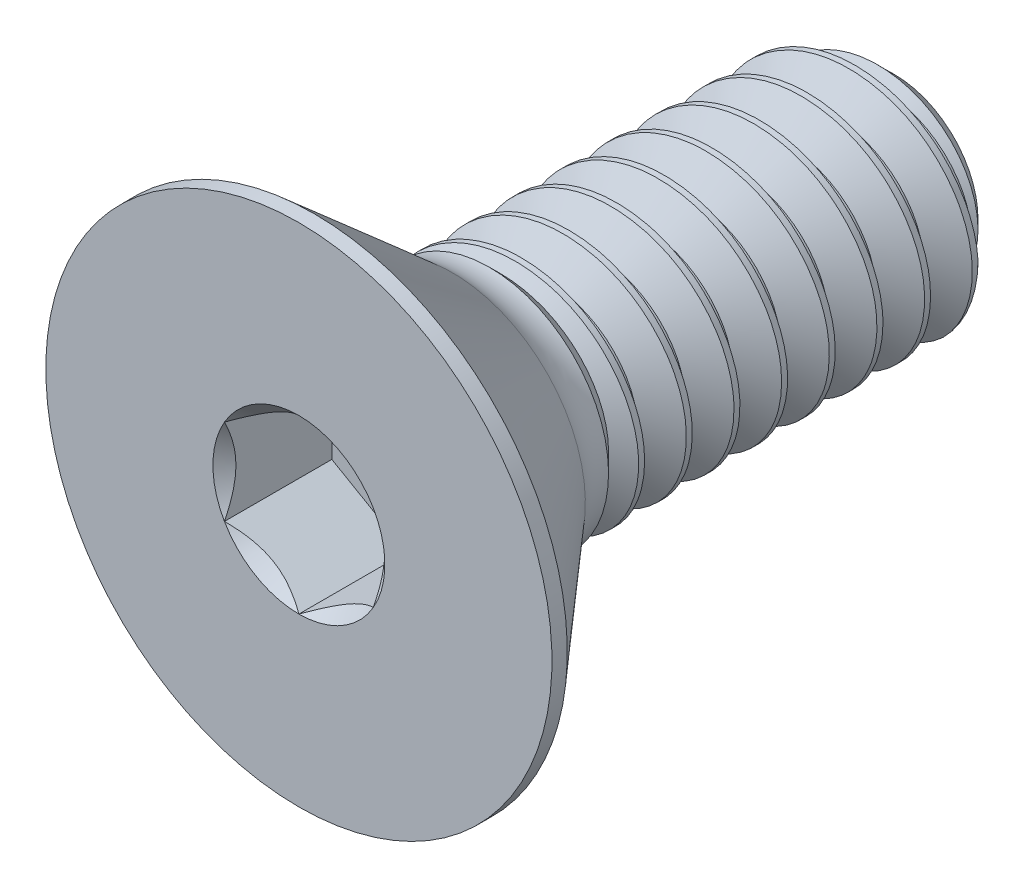
SolidWorks part; units mm, degrees
ref_plane "Front" through (0, 0, 0) normal (0, 0, 1) x (1, 0, 0)
ref_plane "Top" through (0, 0, 0) normal (0, 1, 0) x (1, 0, 0)
ref_plane "Right" through (0, 0, 0) normal (1, 0, 0) x (0, 0, -1)
sketch "Sketch1" plane through (0, 0, 0) normal (1, 0, 0) x (0, 0, -1)
  line L0 (0, 6.7437) -> (0.4089, 6.7437) construction
  line L1 (0.4089, 6.7437) -> (4.0894, 3.5443) construction
  line L2 (0, 3.175) -> (15.875, 3.175)
  line L3 (15.875, 3.175) -> (15.875, 0)
  line L4 (15.875, 0) -> (0, 0)
  line L5 (0, 0) -> (0, 6.7437) construction
  line L6 (0, 6.7437) -> (0, -6.7437) construction
  line L7 (15.875, 3.175) -> (15.875, -3.175) construction
  line L8 (0, -6.7437) -> (0.4089, -6.7437) construction
  line L9 (0.4089, -6.7437) -> (4.0894, -3.5443) construction
  line L11 (0, 3.175) -> (0, 0)
  line L12 (5.0772, 3.175) -> (5.0772, 0) construction
  arc A1 (4.0894, 3.5443) -> (5.0772, 3.175) centre (5.0772, 4.6807) ccw construction
  dimension "D1" = 0.4089
revolve "Revolve1" add sketch "Sketch1" angle 360 mid plane about L4
sketch "Sketch3" plane through (0, 0, -15.875) normal (0, 0, -1) x (-1, 0, 0)
  circle A0 centre (0, 0) radius 3.175
curve "Helix/Spiral1" pitch 1.27 height 15.875 radius 3.175 centre (0, 0, -15.875) axis (0, 0, 1) start towards (0, 1, 0)
sketch "Sketch2" plane through (0, 0, 0) normal (1, 0, 0) x (0, 0, -1)
  line L0 (15.875, 3.175) -> (16.9863, 3.175)
  line L1 (16.9863, 3.175) -> (16.51, 2.3501)
  line L2 (16.51, 2.3501) -> (16.3512, 2.3501)
  line L3 (16.3512, 2.3501) -> (15.875, 3.175)
  line L4 (16.1131, 2.7626) -> (16.7481, 2.7626) construction
  dimension "D1" = 60
  dimension "D2" = 0.1588
  dimension "D3" = 0.635
chamfer "Chamfer1" distance 0.9525 angle 45 1 edges at (0, 3.175, -15.875)
sweep "Cut-Sweep1" cut profiles "Sketch2" path "Helix/Spiral1" align with end faces yes
sketch "Sketch7" plane through (0, 0, 0) normal (1, 0, 0) x (0, 0, -1)
  line L0 (0, 6.7437) -> (0.4089, 6.7437) construction
  line L1 (0.4089, 6.7437) -> (4.0894, 3.5443) construction
  line L2 (0, 6.7437) -> (0.4089, 6.7437)
  line L3 (0.4089, 6.7437) -> (4.0894, 3.5443)
  line L4 (5.0772, 3.175) -> (5.0772, 0) construction
  line L5 (5.0772, 3.175) -> (5.0772, 0)
  line L7 (0, 0) -> (0, 6.7437) construction
  line L8 (0, 0) -> (0, 6.7437)
  line L9 (0, 0) -> (5.0772, 0)
  line L10 (7.4181, 0) -> (-7.4181, 0) construction
  arc A0 (4.0894, 3.5443) -> (5.0772, 3.175) centre (5.0772, 4.6807) ccw construction
  arc A1 (4.0894, 3.5443) -> (5.0772, 3.175) centre (5.0772, 4.6807) ccw
revolve "Revolve2" add sketch "Sketch7" angle 360 mid plane about L9
ref_plane "Plane1" through (0, 0, -5.0772) normal (0, 0, 1) x (1, 0, 0)
sketch "Sketch8" plane through (0, 0, -5.0772) normal (0, 0, 1) x (1, 0, 0)
  circle A0 centre (0, 0) radius 3.175
extrude "Boss-Extrude1" add sketch "Sketch8" against normal through all draft 45
sketch "Sketch11" [suppressed] plane through (0, 0, 0) normal (1, 0, 0) x (0, 0, -1)
  line L0 (4.4996, 0) -> (-4.4996, 0) construction
  line L1 (7.3025, 3.8989) -> (1.7272, 3.8989)
  line L2 (7.3025, 3.8989) -> (7.3025, -3.8989)
  line L3 (7.3025, -3.8989) -> (1.7272, -3.8989)
  line L4 (1.7272, 3.8989) -> (1.7272, -3.8989)
  line L5 (0, 3.8989) -> (0.1727, 3.8989) construction
  line L7 (4.7625, 1.7526) -> (4.7625, 0) construction
  point P4 (1.7272, 0)
  dimension "D1" = 2.54
extrude "Cut-Extrude4" [suppressed] cut sketch "Sketch11" against normal through all and the other way through all
combine bodies "Combine1" operation type add bodies to combine 117 114
sketch "Sketch5" plane through (0, 0, 0) normal (0, 0, 1) x (1, 0, 0)
  line L1 (1.9844, -1.1457) -> (1.9844, 1.1457)
  line L2 (1.9844, 1.1457) -> (0, 2.2914)
  line L3 (0, 2.2914) -> (-1.9844, 1.1457)
  line L4 (-1.9844, 1.1457) -> (-1.9844, -1.1457)
  line L5 (-1.9844, -1.1457) -> (0, -2.2914)
  line L6 (0, -2.2914) -> (1.9844, -1.1457)
  circle A0 centre (0, 0) radius 1.9844 construction
  dimension "Hex" = 3.9688
extrude "Cut-Extrude2" cut sketch "Sketch5" against normal blind 2.8626
sketch "Sketch6" plane through (0, 0, 0) normal (0, 0, 1) x (1, 0, 0)
  circle A0 centre (0, 0) radius 2.2914
extrude "Cut-Extrude3" cut sketch "Sketch6" against normal blind 2.8626 draft 45
sketch "Sketch9" [suppressed] plane through (0, 0, -5.0772) normal (0, 0, 1) x (1, 0, 0)
  circle A1 centre (0, 0) radius 3.175
  circle A2 centre (0, 0) radius 3.175
  point P0 (0, 3.175)
  dimension "D1" = 0
extrude "Boss-Extrude2" [suppressed] add sketch "Sketch9" against normal offset from surface (20.3228 mm away) 44.45 up to face at (0, 2.2225, -15.875)
sketch "Sketch10" plane through (0, 0, 0) normal (1, 0, 0) x (0, 0, -1)
  line L0 (15.875, 3.175) -> (15.875, -3.175) construction
  point P0 (13.97, -3.175)
  dimension "D1" = 1.905
equation "\"D3@Helix/Spiral1\" = \"Lg@Sketch1\""
equation "\"D2@Sketch2\" = \"D4@Helix/Spiral1\" * .125"
equation "\"D3@Sketch2\" = \"D4@Helix/Spiral1\" * .5"
equation "\"D1@Chamfer1\" = \"D4@Helix/Spiral1\" * .75"
equation "\"D1@Cut-Extrude2\" = \"Head Ht@Sketch1\" * .7"
equation "\"D1@Sketch1\" = \"Head Ht@Sketch1\" * .1"
equation "\"D1@Sketch10\" = \"D4@Helix/Spiral1\" * 1.5"
equation "\"D1@Cut-Extrude3\" = \"D1@Cut-Extrude2\""
